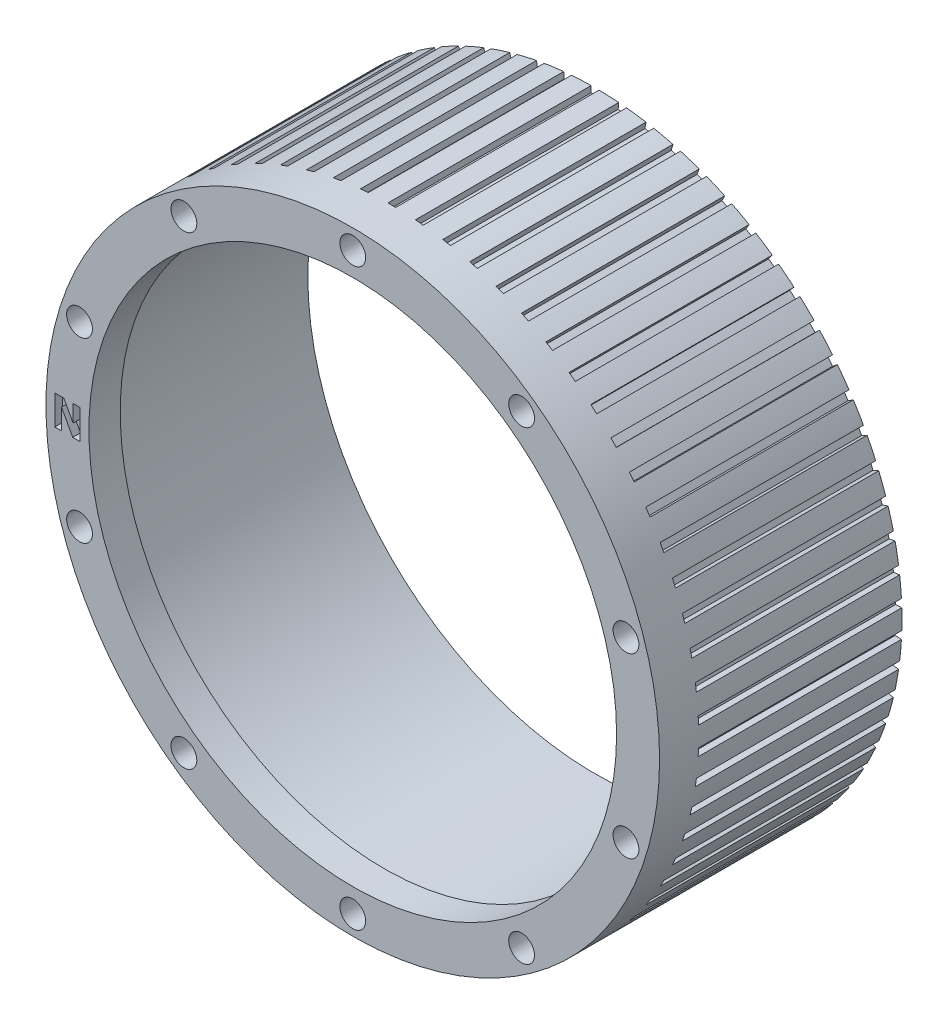
SolidWorks part; units mm, degrees
ref_plane "Front" through (0, 0, 0) normal (0, 0, 1) x (1, 0, 0)
ref_plane "Top" through (0, 0, 0) normal (0, 1, 0) x (1, 0, 0)
ref_plane "Right" through (0, 0, 0) normal (1, 0, 0) x (0, 0, -1)
sketch "Sketch1" plane through (0, 0, 0) normal (0, 0, 1) x (1, 0, 0)
  circle A0 centre (0, 0) radius 36.75 construction
  circle A1 centre (0, 0) radius 39.25
  dimension "D1" = 73.5
  dimension "D2" = 2.5
extrude "Boss-Extrude1" add sketch "Sketch1" along normal blind 31
sketch "Sketch2" plane through (0, 0, 0) normal (0, 0, -1) x (-1, 0, 0)
  circle A0 centre (0, 0) radius 36.75 construction
  circle A1 centre (0, 0) radius 36.75
extrude "Cut-Extrude1" cut sketch "Sketch2" against normal offset from surface (27 mm away) 4 up to face at (39.25, 0, 31)
sketch "Sketch3" plane through (0, 0, 31) normal (0, 0, 1) x (1, 0, 0)
  circle A0 centre (0, 0) radius 36.75 construction
  circle A1 centre (0, 0) radius 36.75 construction
  circle A2 centre (0, 0) radius 33.75
  dimension "D1" = 3
extrude "Cut-Extrude2" cut sketch "Sketch3" against normal up to surface (4 mm away) up to face at (36.75, 0, 27)
sketch "Sketch4" plane through (0, 0, 31) normal (0, 0, 1) x (1, 0, 0)
  line L0 (0, 0) -> (0, 39.25) construction
  circle A0 centre (0, 0) radius 36.75 construction
  circle A1 centre (0, 0) radius 36.75 construction
  circle A2 centre (-34.9513, -11.3564) radius 1.65
  circle A3 centre (0, 0) radius 36.75 construction
  circle A4 centre (-34.9513, 11.3564) radius 1.65
  circle A5 centre (0, 0) radius 36.75 construction
  circle A6 centre (-21.6011, 29.7314) radius 1.65
  circle A7 centre (0, 0) radius 36.75 construction
  circle A8 centre (0, 36.75) radius 1.65
  circle A9 centre (0, 0) radius 36.75 construction
  circle A10 centre (21.6011, 29.7314) radius 1.65
  circle A11 centre (0, 0) radius 36.75 construction
  circle A12 centre (34.9513, 11.3564) radius 1.65
  circle A13 centre (0, 0) radius 36.75 construction
  circle A14 centre (34.9513, -11.3564) radius 1.65
  circle A15 centre (0, 0) radius 36.75 construction
  circle A16 centre (21.6011, -29.7314) radius 1.65
  circle A17 centre (0, 0) radius 36.75 construction
  circle A18 centre (0, -36.75) radius 1.65
  circle A19 centre (0, 0) radius 36.75 construction
  circle A20 centre (-21.6011, -29.7314) radius 1.65
  circle A21 centre (0, 0) radius 39.25 construction
  dimension "D1" = 3.3
  dimension "D3" = 21.6011
  dimension "D2" = 10
extrude "Cut-Extrude3" cut sketch "Sketch4" against normal blind 3
sketch "Sketch5" plane through (0, 0, 0) normal (0, 0, -1) x (-1, 0, 0)
  line L0 (0, 0) -> (0, 39.25) construction
  line L1 (-0.5, 39.25) -> (0.5, 39.25)
  line L2 (-0.5, 39.25) -> (-0.5, 38.45)
  line L3 (-0.5, 38.45) -> (0.5, 38.45)
  line L4 (0.5, 39.25) -> (0.5, 38.45)
  line L5 (-0.5, 39.25) -> (0.5, 38.45) construction
  line L6 (-0.5, 38.45) -> (0.5, 39.25) construction
  line L7 (3.0204, 39.1368) -> (2.9486, 38.34)
  line L8 (3.0204, 39.1368) -> (4.0163, 39.0472)
  line L9 (4.0163, 39.0472) -> (3.9446, 38.2504)
  line L10 (2.9486, 38.34) -> (3.9446, 38.2504)
  line L11 (6.5164, 38.7085) -> (6.3735, 37.9214)
  line L12 (6.5164, 38.7085) -> (7.5003, 38.53)
  line L13 (7.5003, 38.53) -> (7.3575, 37.7428)
  line L14 (6.3735, 37.9214) -> (7.3575, 37.7428)
  line L15 (9.96, 37.9686) -> (9.7471, 37.1974)
  line L16 (9.96, 37.9686) -> (10.9239, 37.7025)
  line L17 (10.9239, 37.7025) -> (10.7111, 36.9314)
  line L18 (9.7471, 37.1974) -> (10.7111, 36.9314)
  line L19 (13.3233, 36.9229) -> (13.0422, 36.1739)
  line L20 (13.3233, 36.9229) -> (14.2596, 36.5715)
  line L21 (14.2596, 36.5715) -> (13.9785, 35.8225)
  line L22 (13.0422, 36.1739) -> (13.9785, 35.8225)
  line L23 (16.5795, 35.58) -> (16.2323, 34.8592)
  line L24 (16.5795, 35.58) -> (17.4804, 35.1461)
  line L25 (17.4804, 35.1461) -> (17.1333, 34.4253)
  line L26 (16.2323, 34.8592) -> (17.1333, 34.4253)
  line L27 (19.7021, 33.9506) -> (19.2918, 33.2638)
  line L28 (19.7021, 33.9506) -> (20.5605, 33.4377)
  line L29 (20.5605, 33.4377) -> (20.1502, 32.7509)
  line L30 (19.2918, 33.2638) -> (20.1502, 32.7509)
  line L31 (22.6661, 32.0478) -> (22.1958, 31.4006)
  line L32 (22.6661, 32.0478) -> (23.4751, 31.46)
  line L33 (23.4751, 31.46) -> (23.0049, 30.8128)
  line L34 (22.1958, 31.4006) -> (23.0049, 30.8128)
  line L35 (25.4476, 29.887) -> (24.9212, 29.2846)
  line L36 (25.4476, 29.887) -> (26.2006, 29.2291)
  line L37 (26.2006, 29.2291) -> (25.6743, 28.6266)
  line L38 (24.9212, 29.2846) -> (25.6743, 28.6266)
  line L39 (28.0242, 27.4856) -> (27.4459, 26.9328)
  line L40 (28.0242, 27.4856) -> (28.7152, 26.7628)
  line L41 (28.7152, 26.7628) -> (28.137, 26.21)
  line L42 (27.4459, 26.9328) -> (28.137, 26.21)
  line L43 (30.3751, 24.8629) -> (29.7497, 24.3641)
  line L44 (30.3751, 24.8629) -> (30.9986, 24.0811)
  line L45 (30.9986, 24.0811) -> (30.3732, 23.5823)
  line L46 (29.7497, 24.3641) -> (30.3732, 23.5823)
  line L47 (32.4816, 22.04) -> (31.8139, 21.5993)
  line L48 (32.4816, 22.04) -> (33.0324, 21.2054)
  line L49 (33.0324, 21.2054) -> (32.3648, 20.7647)
  line L50 (31.8139, 21.5993) -> (32.3648, 20.7647)
  line L51 (34.3264, 19.0396) -> (33.622, 18.6605)
  line L52 (34.3264, 19.0396) -> (34.8003, 18.159)
  line L53 (34.8003, 18.159) -> (34.0958, 17.78)
  line L54 (33.622, 18.6605) -> (34.0958, 17.78)
  line L55 (35.895, 15.886) -> (35.1593, 15.5716)
  line L56 (35.895, 15.886) -> (36.288, 14.9665)
  line L57 (36.288, 14.9665) -> (35.5524, 14.652)
  line L58 (35.1593, 15.5716) -> (35.5524, 14.652)
  line L59 (37.1745, 12.6044) -> (36.4136, 12.3572)
  line L60 (37.1745, 12.6044) -> (37.4835, 11.6534)
  line L61 (37.4835, 11.6534) -> (36.7226, 11.4062)
  line L62 (36.4136, 12.3572) -> (36.7226, 11.4062)
  line L63 (38.1547, 9.2214) -> (37.3747, 9.0434)
  line L64 (38.1547, 9.2214) -> (38.3772, 8.2465)
  line L65 (38.3772, 8.2465) -> (37.5972, 8.0685)
  line L66 (37.3747, 9.0434) -> (37.5972, 8.0685)
  line L67 (38.8277, 5.7641) -> (38.0349, 5.6567)
  line L68 (38.8277, 5.7641) -> (38.9619, 4.7732)
  line L69 (38.9619, 4.7732) -> (38.1691, 4.6658)
  line L70 (38.0349, 5.6567) -> (38.1691, 4.6658)
  line L71 (39.188, 2.2604) -> (38.3889, 2.2245)
  line L72 (39.188, 2.2604) -> (39.2329, 1.2614)
  line L73 (39.2329, 1.2614) -> (38.4337, 1.2256)
  line L74 (38.3889, 2.2245) -> (38.4337, 1.2256)
  line L75 (39.2329, -1.2614) -> (38.4337, -1.2256)
  line L76 (39.2329, -1.2614) -> (39.188, -2.2604)
  line L77 (39.188, -2.2604) -> (38.3889, -2.2245)
  line L78 (38.4337, -1.2256) -> (38.3889, -2.2245)
  line L79 (38.9619, -4.7732) -> (38.1691, -4.6658)
  line L80 (38.9619, -4.7732) -> (38.8277, -5.7641)
  line L81 (38.8277, -5.7641) -> (38.0349, -5.6567)
  line L82 (38.1691, -4.6658) -> (38.0349, -5.6567)
  line L83 (38.3772, -8.2465) -> (37.5972, -8.0685)
  line L84 (38.3772, -8.2465) -> (38.1547, -9.2214)
  line L85 (38.1547, -9.2214) -> (37.3747, -9.0434)
  line L86 (37.5972, -8.0685) -> (37.3747, -9.0434)
  line L87 (37.4835, -11.6534) -> (36.7226, -11.4062)
  line L88 (37.4835, -11.6534) -> (37.1745, -12.6044)
  line L89 (37.1745, -12.6044) -> (36.4136, -12.3572)
  line L90 (36.7226, -11.4062) -> (36.4136, -12.3572)
  line L91 (36.288, -14.9665) -> (35.5524, -14.652)
  line L92 (36.288, -14.9665) -> (35.895, -15.886)
  line L93 (35.895, -15.886) -> (35.1593, -15.5716)
  line L94 (35.5524, -14.652) -> (35.1593, -15.5716)
  line L95 (34.8003, -18.159) -> (34.0958, -17.78)
  line L96 (34.8003, -18.159) -> (34.3264, -19.0396)
  line L97 (34.3264, -19.0396) -> (33.622, -18.6605)
  line L98 (34.0958, -17.78) -> (33.622, -18.6605)
  line L99 (33.0324, -21.2054) -> (32.3648, -20.7647)
  line L100 (33.0324, -21.2054) -> (32.4816, -22.04)
  line L101 (32.4816, -22.04) -> (31.8139, -21.5993)
  line L102 (32.3648, -20.7647) -> (31.8139, -21.5993)
  line L103 (30.9986, -24.0811) -> (30.3732, -23.5823)
  line L104 (30.9986, -24.0811) -> (30.3751, -24.8629)
  line L105 (30.3751, -24.8629) -> (29.7497, -24.3641)
  line L106 (30.3732, -23.5823) -> (29.7497, -24.3641)
  line L107 (28.7152, -26.7628) -> (28.137, -26.21)
  line L108 (28.7152, -26.7628) -> (28.0242, -27.4856)
  line L109 (28.0242, -27.4856) -> (27.4459, -26.9328)
  line L110 (28.137, -26.21) -> (27.4459, -26.9328)
  line L111 (26.2006, -29.2291) -> (25.6743, -28.6266)
  line L112 (26.2006, -29.2291) -> (25.4476, -29.887)
  line L113 (25.4476, -29.887) -> (24.9212, -29.2846)
  line L114 (25.6743, -28.6266) -> (24.9212, -29.2846)
  line L115 (23.4751, -31.46) -> (23.0049, -30.8128)
  line L116 (23.4751, -31.46) -> (22.6661, -32.0478)
  line L117 (22.6661, -32.0478) -> (22.1958, -31.4006)
  line L118 (23.0049, -30.8128) -> (22.1958, -31.4006)
  line L119 (20.5605, -33.4377) -> (20.1502, -32.7509)
  line L120 (20.5605, -33.4377) -> (19.7021, -33.9506)
  line L121 (19.7021, -33.9506) -> (19.2918, -33.2638)
  line L122 (20.1502, -32.7509) -> (19.2918, -33.2638)
  line L123 (17.4804, -35.1461) -> (17.1333, -34.4253)
  line L124 (17.4804, -35.1461) -> (16.5795, -35.58)
  line L125 (16.5795, -35.58) -> (16.2323, -34.8592)
  line L126 (17.1333, -34.4253) -> (16.2323, -34.8592)
  line L127 (14.2596, -36.5715) -> (13.9785, -35.8225)
  line L128 (14.2596, -36.5715) -> (13.3233, -36.9229)
  line L129 (13.3233, -36.9229) -> (13.0422, -36.1739)
  line L130 (13.9785, -35.8225) -> (13.0422, -36.1739)
  line L131 (10.9239, -37.7025) -> (10.7111, -36.9314)
  line L132 (10.9239, -37.7025) -> (9.96, -37.9686)
  line L133 (9.96, -37.9686) -> (9.7471, -37.1974)
  line L134 (10.7111, -36.9314) -> (9.7471, -37.1974)
  line L135 (7.5003, -38.53) -> (7.3575, -37.7428)
  line L136 (7.5003, -38.53) -> (6.5164, -38.7085)
  line L137 (6.5164, -38.7085) -> (6.3735, -37.9214)
  line L138 (7.3575, -37.7428) -> (6.3735, -37.9214)
  line L139 (4.0163, -39.0472) -> (3.9446, -38.2504)
  line L140 (4.0163, -39.0472) -> (3.0204, -39.1368)
  line L141 (3.0204, -39.1368) -> (2.9486, -38.34)
  line L142 (3.9446, -38.2504) -> (2.9486, -38.34)
  line L143 (0.5, -39.25) -> (0.5, -38.45)
  line L144 (0.5, -39.25) -> (-0.5, -39.25)
  line L145 (-0.5, -39.25) -> (-0.5, -38.45)
  line L146 (0.5, -38.45) -> (-0.5, -38.45)
  line L147 (-3.0204, -39.1368) -> (-2.9486, -38.34)
  line L148 (-3.0204, -39.1368) -> (-4.0163, -39.0472)
  line L149 (-4.0163, -39.0472) -> (-3.9446, -38.2504)
  line L150 (-2.9486, -38.34) -> (-3.9446, -38.2504)
  line L151 (-6.5164, -38.7085) -> (-6.3735, -37.9214)
  line L152 (-6.5164, -38.7085) -> (-7.5003, -38.53)
  line L153 (-7.5003, -38.53) -> (-7.3575, -37.7428)
  line L154 (-6.3735, -37.9214) -> (-7.3575, -37.7428)
  line L155 (-9.96, -37.9686) -> (-9.7471, -37.1974)
  line L156 (-9.96, -37.9686) -> (-10.9239, -37.7025)
  line L157 (-10.9239, -37.7025) -> (-10.7111, -36.9314)
  line L158 (-9.7471, -37.1974) -> (-10.7111, -36.9314)
  line L159 (-13.3233, -36.9229) -> (-13.0422, -36.1739)
  line L160 (-13.3233, -36.9229) -> (-14.2596, -36.5715)
  line L161 (-14.2596, -36.5715) -> (-13.9785, -35.8225)
  line L162 (-13.0422, -36.1739) -> (-13.9785, -35.8225)
  line L163 (-16.5795, -35.58) -> (-16.2323, -34.8592)
  line L164 (-16.5795, -35.58) -> (-17.4804, -35.1461)
  line L165 (-17.4804, -35.1461) -> (-17.1333, -34.4253)
  line L166 (-16.2323, -34.8592) -> (-17.1333, -34.4253)
  line L167 (-19.7021, -33.9506) -> (-19.2918, -33.2638)
  line L168 (-19.7021, -33.9506) -> (-20.5605, -33.4377)
  line L169 (-20.5605, -33.4377) -> (-20.1502, -32.7509)
  line L170 (-19.2918, -33.2638) -> (-20.1502, -32.7509)
  line L171 (-22.6661, -32.0478) -> (-22.1958, -31.4006)
  line L172 (-22.6661, -32.0478) -> (-23.4751, -31.46)
  line L173 (-23.4751, -31.46) -> (-23.0049, -30.8128)
  line L174 (-22.1958, -31.4006) -> (-23.0049, -30.8128)
  line L175 (-25.4476, -29.887) -> (-24.9212, -29.2846)
  line L176 (-25.4476, -29.887) -> (-26.2006, -29.2291)
  line L177 (-26.2006, -29.2291) -> (-25.6743, -28.6266)
  line L178 (-24.9212, -29.2846) -> (-25.6743, -28.6266)
  line L179 (-28.0242, -27.4856) -> (-27.4459, -26.9328)
  line L180 (-28.0242, -27.4856) -> (-28.7152, -26.7628)
  line L181 (-28.7152, -26.7628) -> (-28.137, -26.21)
  line L182 (-27.4459, -26.9328) -> (-28.137, -26.21)
  line L183 (-30.3751, -24.8629) -> (-29.7497, -24.3641)
  line L184 (-30.3751, -24.8629) -> (-30.9986, -24.0811)
  line L185 (-30.9986, -24.0811) -> (-30.3732, -23.5823)
  line L186 (-29.7497, -24.3641) -> (-30.3732, -23.5823)
  line L187 (-32.4816, -22.04) -> (-31.8139, -21.5993)
  line L188 (-32.4816, -22.04) -> (-33.0324, -21.2054)
  line L189 (-33.0324, -21.2054) -> (-32.3648, -20.7647)
  line L190 (-31.8139, -21.5993) -> (-32.3648, -20.7647)
  line L191 (-34.3264, -19.0396) -> (-33.622, -18.6605)
  line L192 (-34.3264, -19.0396) -> (-34.8003, -18.159)
  line L193 (-34.8003, -18.159) -> (-34.0958, -17.78)
  line L194 (-33.622, -18.6605) -> (-34.0958, -17.78)
  line L195 (-35.895, -15.886) -> (-35.1593, -15.5716)
  line L196 (-35.895, -15.886) -> (-36.288, -14.9665)
  line L197 (-36.288, -14.9665) -> (-35.5524, -14.652)
  line L198 (-35.1593, -15.5716) -> (-35.5524, -14.652)
  line L199 (-37.1745, -12.6044) -> (-36.4136, -12.3572)
  line L200 (-37.1745, -12.6044) -> (-37.4835, -11.6534)
  line L201 (-37.4835, -11.6534) -> (-36.7226, -11.4062)
  line L202 (-36.4136, -12.3572) -> (-36.7226, -11.4062)
  line L203 (-38.1547, -9.2214) -> (-37.3747, -9.0434)
  line L204 (-38.1547, -9.2214) -> (-38.3772, -8.2465)
  line L205 (-38.3772, -8.2465) -> (-37.5972, -8.0685)
  line L206 (-37.3747, -9.0434) -> (-37.5972, -8.0685)
  line L207 (-38.8277, -5.7641) -> (-38.0349, -5.6567)
  line L208 (-38.8277, -5.7641) -> (-38.9619, -4.7732)
  line L209 (-38.9619, -4.7732) -> (-38.1691, -4.6658)
  line L210 (-38.0349, -5.6567) -> (-38.1691, -4.6658)
  line L211 (-39.188, -2.2604) -> (-38.3889, -2.2245)
  line L212 (-39.188, -2.2604) -> (-39.2329, -1.2614)
  line L213 (-39.2329, -1.2614) -> (-38.4337, -1.2256)
  line L214 (-38.3889, -2.2245) -> (-38.4337, -1.2256)
  line L215 (-39.2329, 1.2614) -> (-38.4337, 1.2256)
  line L216 (-39.2329, 1.2614) -> (-39.188, 2.2604)
  line L217 (-39.188, 2.2604) -> (-38.3889, 2.2245)
  line L218 (-38.4337, 1.2256) -> (-38.3889, 2.2245)
  line L219 (-38.9619, 4.7732) -> (-38.1691, 4.6658)
  line L220 (-38.9619, 4.7732) -> (-38.8277, 5.7641)
  line L221 (-38.8277, 5.7641) -> (-38.0349, 5.6567)
  line L222 (-38.1691, 4.6658) -> (-38.0349, 5.6567)
  line L223 (-38.3772, 8.2465) -> (-37.5972, 8.0685)
  line L224 (-38.3772, 8.2465) -> (-38.1547, 9.2214)
  line L225 (-38.1547, 9.2214) -> (-37.3747, 9.0434)
  line L226 (-37.5972, 8.0685) -> (-37.3747, 9.0434)
  line L227 (-37.4835, 11.6534) -> (-36.7226, 11.4062)
  line L228 (-37.4835, 11.6534) -> (-37.1745, 12.6044)
  line L229 (-37.1745, 12.6044) -> (-36.4136, 12.3572)
  line L230 (-36.7226, 11.4062) -> (-36.4136, 12.3572)
  line L231 (-36.288, 14.9665) -> (-35.5524, 14.652)
  line L232 (-36.288, 14.9665) -> (-35.895, 15.886)
  line L233 (-35.895, 15.886) -> (-35.1593, 15.5716)
  line L234 (-35.5524, 14.652) -> (-35.1593, 15.5716)
  line L235 (-34.8003, 18.159) -> (-34.0958, 17.78)
  line L236 (-34.8003, 18.159) -> (-34.3264, 19.0396)
  line L237 (-34.3264, 19.0396) -> (-33.622, 18.6605)
  line L238 (-34.0958, 17.78) -> (-33.622, 18.6605)
  line L239 (-33.0324, 21.2054) -> (-32.3648, 20.7647)
  line L240 (-33.0324, 21.2054) -> (-32.4816, 22.04)
  line L241 (-32.4816, 22.04) -> (-31.8139, 21.5993)
  line L242 (-32.3648, 20.7647) -> (-31.8139, 21.5993)
  line L243 (-30.9986, 24.0811) -> (-30.3732, 23.5823)
  line L244 (-30.9986, 24.0811) -> (-30.3751, 24.8629)
  line L245 (-30.3751, 24.8629) -> (-29.7497, 24.3641)
  line L246 (-30.3732, 23.5823) -> (-29.7497, 24.3641)
  line L247 (-28.7152, 26.7628) -> (-28.137, 26.21)
  line L248 (-28.7152, 26.7628) -> (-28.0242, 27.4856)
  line L249 (-28.0242, 27.4856) -> (-27.4459, 26.9328)
  line L250 (-28.137, 26.21) -> (-27.4459, 26.9328)
  line L251 (-26.2006, 29.2291) -> (-25.6743, 28.6266)
  line L252 (-26.2006, 29.2291) -> (-25.4476, 29.887)
  line L253 (-25.4476, 29.887) -> (-24.9212, 29.2846)
  line L254 (-25.6743, 28.6266) -> (-24.9212, 29.2846)
  line L255 (-23.4751, 31.46) -> (-23.0049, 30.8128)
  line L256 (-23.4751, 31.46) -> (-22.6661, 32.0478)
  line L257 (-22.6661, 32.0478) -> (-22.1958, 31.4006)
  line L258 (-23.0049, 30.8128) -> (-22.1958, 31.4006)
  line L259 (-20.5605, 33.4377) -> (-20.1502, 32.7509)
  line L260 (-20.5605, 33.4377) -> (-19.7021, 33.9506)
  line L261 (-19.7021, 33.9506) -> (-19.2918, 33.2638)
  line L262 (-20.1502, 32.7509) -> (-19.2918, 33.2638)
  line L263 (-17.4804, 35.1461) -> (-17.1333, 34.4253)
  line L264 (-17.4804, 35.1461) -> (-16.5795, 35.58)
  line L265 (-16.5795, 35.58) -> (-16.2323, 34.8592)
  line L266 (-17.1333, 34.4253) -> (-16.2323, 34.8592)
  line L267 (-14.2596, 36.5715) -> (-13.9785, 35.8225)
  line L268 (-14.2596, 36.5715) -> (-13.3233, 36.9229)
  line L269 (-13.3233, 36.9229) -> (-13.0422, 36.1739)
  line L270 (-13.9785, 35.8225) -> (-13.0422, 36.1739)
  line L271 (-10.9239, 37.7025) -> (-10.7111, 36.9314)
  line L272 (-10.9239, 37.7025) -> (-9.96, 37.9686)
  line L273 (-9.96, 37.9686) -> (-9.7471, 37.1974)
  line L274 (-10.7111, 36.9314) -> (-9.7471, 37.1974)
  line L275 (-7.5003, 38.53) -> (-7.3575, 37.7428)
  line L276 (-7.5003, 38.53) -> (-6.5164, 38.7085)
  line L277 (-6.5164, 38.7085) -> (-6.3735, 37.9214)
  line L278 (-7.3575, 37.7428) -> (-6.3735, 37.9214)
  line L279 (-4.0163, 39.0472) -> (-3.9446, 38.2504)
  line L280 (-4.0163, 39.0472) -> (-3.0204, 39.1368)
  line L281 (-3.0204, 39.1368) -> (-2.9486, 38.34)
  line L282 (-3.9446, 38.2504) -> (-2.9486, 38.34)
  circle A1 centre (0, 0) radius 39.25 construction
  point P0 (0, 38.85)
  point P10 (0, 39.25)
  dimension "D1" = 0.8
  dimension "D2" = 1
  dimension "D3" = 70
extrude "Cut-Extrude4" cut sketch "Sketch5" against normal offset from surface (26 mm away) 5 up to face at (1.65, -36.75, 31)
sketch "Sketch6" plane through (0, 0, 31) normal (0, 0, 1) x (1, 0, 0)
  text T0 "N" font "Tahoma" height in points 14
extrude "Cut-Extrude5" cut sketch "Sketch6" against normal blind 1
